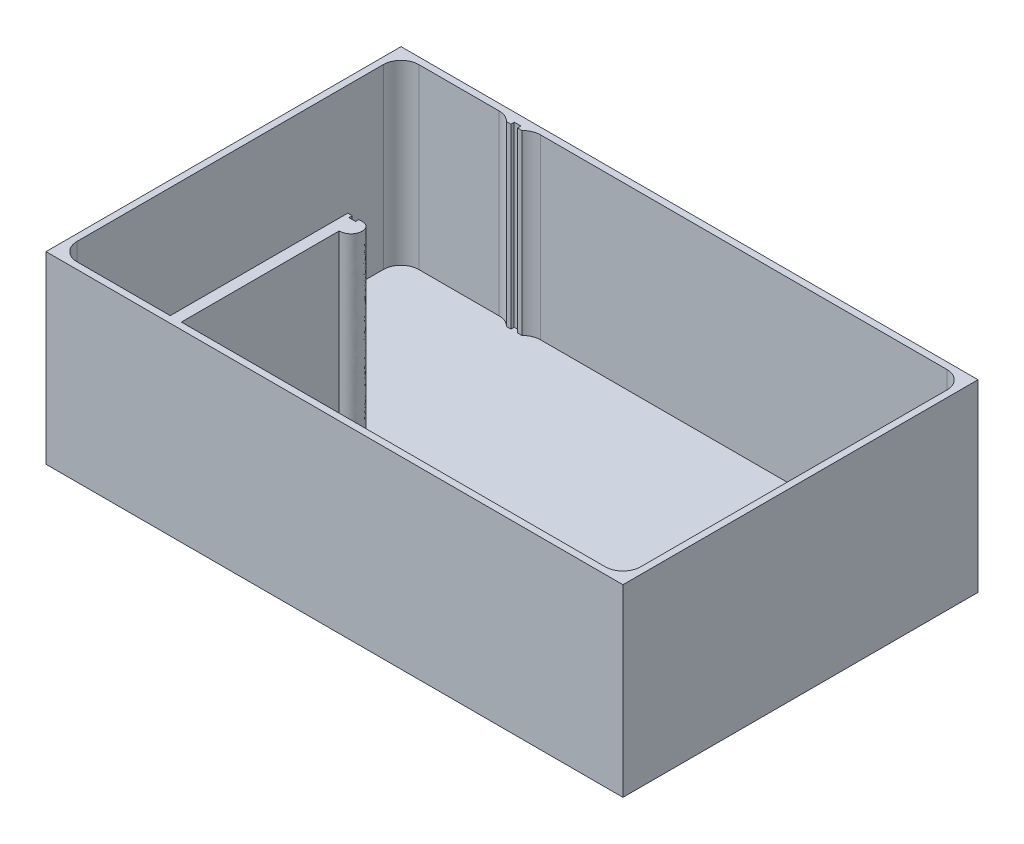
SolidWorks part; units mm, degrees
ref_plane "Ebene vorne" through (0, 0, 0) normal (0, 0, 1) x (1, 0, 0)
ref_plane "Ebene oben" through (0, 0, 0) normal (0, 1, 0) x (1, 0, 0)
ref_plane "Ebene rechts" through (0, 0, 0) normal (1, 0, 0) x (0, 0, -1)
sketch "Sketch1" plane through (0, 0, 0) normal (0, 1, 0) x (1, 0, 0)
  line L1 (-130, -80) -> (130, -80)
  line L2 (-130, -80) -> (-130, 80)
  line L3 (-130, 80) -> (130, 80)
  line L4 (130, -80) -> (130, 80)
  line L5 (-130, -80) -> (130, 80) construction
  line L6 (-130, 80) -> (130, -80) construction
  point P0 (0, 0)
  dimension "D1" = 260
  dimension "D2" = 160
extrude "Boss-Extrude1" add sketch "Sketch1" against normal blind 3
sketch "Sketch2" plane through (0, 0, 0) normal (0, 1, 0) x (1, 0, 0)
  line L4 (130, -80) -> (130, 80)
  line L5 (130, 80) -> (-130, 80)
  line L6 (-130, 80) -> (-130, -80)
  line L7 (-130, -80) -> (130, -80)
  line L8 (130, -80) -> (130, 80)
  line L9 (130, 80) -> (-130, 80)
  line L10 (-130, 80) -> (-130, -80)
  line L11 (-130, -80) -> (130, -80)
  dimension "D1" = 0
extrude "Extrude-Thin2" add sketch "Sketch2" along normal blind 80 thin thin type one direction reverse wall 3
fillet "Fillet1" radius 8 4 edges at (127, 40, 77) (127, 40, -77) (-127, 40, 77) (-127, 40, -77)
sketch "Sketch3" plane through (0, 0, 0) normal (0, 1, 0) x (1, 0, 0)
  line L0 (-119, -77) -> (119, -77) construction
  line L1 (-77, -77) -> (-72, -77)
  line L2 (-77, -77) -> (-77, 3)
  line L4 (-72, -77) -> (-72, -5.9012)
  line L5 (-127, 69) -> (-127, -69) construction
  line L8 (-77, 3) -> (-75, 3)
  line L9 (-75, 3) -> (-75, 1.5)
  line L10 (-75, 1.5) -> (-72, 1.5)
  line L11 (-72, 1.5) -> (-72, 3)
  line L12 (-72, 3) -> (-70, 3)
  spline S0 degree 3 poles (-72, -5.9012) (-65.4058, -5.4857) (-65.3292, 2.681) (-70, 3) knots 0 0 0 0 1 1 1 1
  dimension "D1" = 50
  dimension "D2" = 2
  dimension "D3" = 80
  dimension "D5" = 3
  dimension "D6" = 2
  dimension "D9" = 5
  dimension "D10" = 1.5
extrude "Boss-Extrude2" add sketch "Sketch3" along normal up to surface (80 mm away) up to face at (0, 80, 0)
sketch "Sketch4" plane through (0, 0, 0) normal (0, 1, 0) x (1, 0, 0)
  line L0 (-73.5, 1.5) -> (-73.5, 77) construction
  line L1 (-73.5, 39.25) -> (-68.4781, 39.25) construction
  line L2 (-70, 77) -> (-70, 74.5)
  line L3 (-70, 74.5) -> (-72, 74.5)
  line L4 (-72, 74.5) -> (-72, 76)
  line L5 (-72, 76) -> (-75, 76)
  line L6 (-75, 76) -> (-75, 74.5)
  line L7 (-75, 74.5) -> (-77, 74.5)
  line L8 (-77, 74.5) -> (-77, 77)
  line L9 (-70, 77) -> (-77, 77)
  line L10 (-72, 1.5) -> (-75, 1.5) construction
  line L11 (119, 77) -> (-119, 77) construction
  point P12 (-73.5, 76)
  point P13 (0, 0)
  point P16 (0, 0)
  point P17 (-79.5866, 124.2359)
  point P18 (0, 0)
  point P19 (-79.0046, 125.3999)
  point P20 (-83.2903, 126.5111)
  point P21 (-66.7293, 123.8655)
  point P22 (-80.4861, 123.9714)
  point P23 (-75.0363, 123.9184)
  point P24 (0, 0)
  point P25 (0, 0)
  dimension "D1" = 1.5
  dimension "D2" = 2.5
  dimension "D3" = 2
extrude "Boss-Extrude3" add sketch "Sketch4" along normal up to surface (80 mm away) up to face at (0, 80, 0)
fillet "Fillet2" radius 8 2 edges at (-77, 40, -77) (-70, 40, -77)
